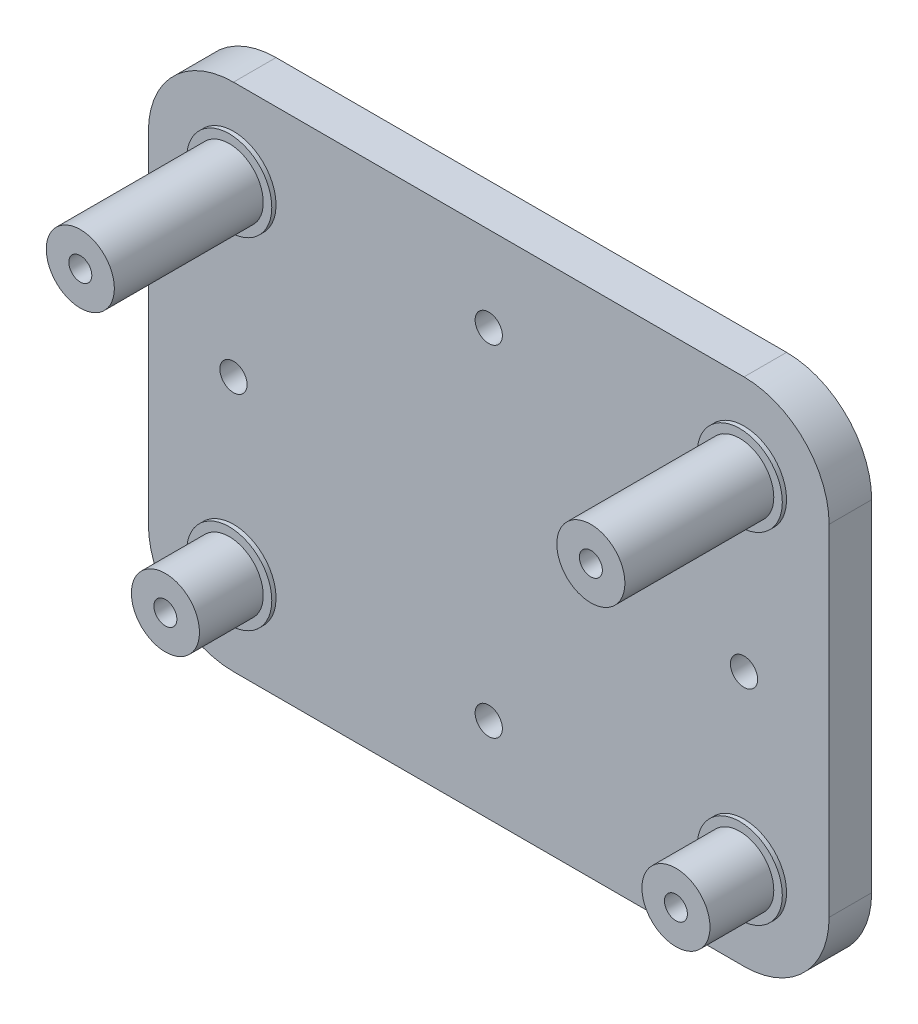
SolidWorks part; units mm, degrees
ref_plane "Front Plane" through (0, 0, 0) normal (0, 0, 1) x (1, 0, 0)
ref_plane "Top Plane" through (0, 0, 0) normal (0, 1, 0) x (1, 0, 0)
ref_plane "Right Plane" through (0, 0, 0) normal (1, 0, 0) x (0, 0, -1)
ref_axis "X" through (-88.99, 0, 0) along (1, 0, 0)
ref_axis "Y" through (0, 55, 0) along (0, -1, 0)
ref_axis "Z" through (0, 0, -88.99) along (0, 0, 1)
sketch "Sketch1" plane through (0, 0, 0) normal (0, 0, 1) x (1, 0, 0)
  line L1 (-30, 20) -> (30, 20) construction
  line L2 (-30, 20) -> (-30, -20) construction
  line L3 (-30, -20) -> (30, -20) construction
  line L4 (30, 20) -> (30, -20) construction
  line L5 (-30, 20) -> (30, -20) construction
  line L6 (-30, -20) -> (30, 20) construction
  line L7 (-40, 30) -> (40, 30)
  line L8 (-40, 30) -> (-40, -30)
  line L9 (-40, -30) -> (40, -30)
  line L10 (40, 30) -> (40, -30)
  line L11 (-40, 30) -> (40, -30) construction
  line L12 (-40, -30) -> (40, 30) construction
  circle A0 centre (-30, 20) radius 4
  circle A1 centre (-30, -20) radius 4
  circle A2 centre (30, -20) radius 4
  circle A3 centre (30, 20) radius 4
  circle A4 centre (-30, 20) radius 5
  circle A5 centre (30, 20) radius 5
  circle A6 centre (30, -20) radius 5
  circle A7 centre (-30, -20) radius 5
  circle A8 centre (-30, 20) radius 1.35
  circle A9 centre (-30, -20) radius 1.35
  circle A10 centre (30, 20) radius 1.35
  circle A11 centre (30, -20) radius 1.35
  circle A12 centre (-30, 0) radius 1.6
  circle A13 centre (0, 20) radius 1.6
  circle A14 centre (30, 0) radius 1.6
  circle A15 centre (0, -20) radius 1.6
  point P0 (0, 0)
  point P10 (0, 0)
  dimension "D1" = 40
  dimension "D3" = 8
  dimension "D6" = 1
  dimension "D7" = 2.7
  dimension "D8" = 3.2
  dimension "D2" = 60
  dimension "D4" = 10
  dimension "D5" = 10
extrude "Boss-Extrude1" add sketch "Sketch1" against normal blind 5 contours L8 L9 L10 L7
extrude "Boss-Extrude2" add sketch "Sketch1<3>" along normal blind 8 contours A1 A9 | A2 A11 region at (-33.8869, -20, 0) region at (26.1131, -20, 0)
sketch "Sketch1<3>" plane through (0, 0, 0) normal (0, 0, 1) x (1, 0, 0) same geometry as "Sketch1"
extrude "Boss-Extrude4" add sketch "Sketch1<5>" along normal blind 18 contours A0 A8 | A3 A10 region at (-33.8869, 20, 0) region at (26.1131, 20, 0)
sketch "Sketch1<5>" plane through (0, 0, 0) normal (0, 0, 1) x (1, 0, 0) same geometry as "Sketch1"
extrude "Boss-Extrude3" add sketch "Sketch1<4>" along normal blind 0.5 contours A4 A0 | A5 A3 | A6 A2 | A7 A1 region at (-34.8586, 20, 0) region at (25.1414, 20, 0) region at (25.1414, -20, 0) region at (-34.8586, -20, 0)
sketch "Sketch1<4>" plane through (0, 0, 0) normal (0, 0, 1) x (1, 0, 0) same geometry as "Sketch1"
extrude "Cut-Extrude1" cut sketch "Sketch1<6>" against normal through all both and the other way through all contours A13 | A12 | A15 | A14 region at (-30, 0, 0) region at (0, 20, 0) region at (30, 0, 0) region at (0, -20, 0)
sketch "Sketch1<6>" plane through (0, 0, 0) normal (0, 0, 1) x (1, 0, 0) same geometry as "Sketch1"
fillet "Fillet1" radius 10 4 edges at (40, 30, -2.5) (40, -30, -2.5) (-40, -30, -2.5) (-40, 30, -2.5)
